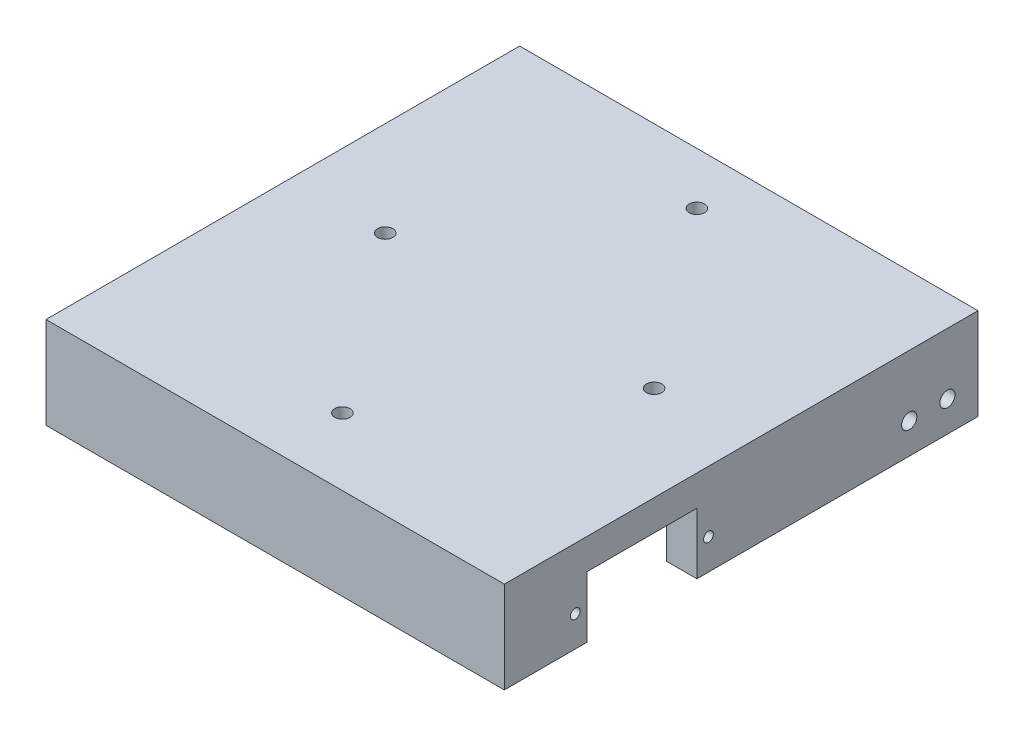
SolidWorks part; units mm, degrees
ref_plane "Front Plane" through (0, 0, 0) normal (0, 0, 1) x (1, 0, 0)
ref_plane "Top Plane" through (0, 0, 0) normal (0, 1, 0) x (1, 0, 0)
ref_plane "Right Plane" through (0, 0, 0) normal (1, 0, 0) x (0, 0, -1)
sketch "Sketch1" plane through (0, 0, 0) normal (0, 1, 0) x (1, 0, 0)
  line L1 (-47.625, -47.625) -> (47.625, -47.625)
  line L2 (-47.625, -47.625) -> (-47.625, 47.625)
  line L3 (-47.625, 47.625) -> (47.625, 47.625)
  line L4 (47.625, -47.625) -> (47.625, 47.625)
  line L5 (-47.625, -47.625) -> (47.625, 47.625) construction
  line L6 (-47.625, 47.625) -> (47.625, -47.625) construction
  point P0 (0, 0)
  dimension "D1" = 95.25
  dimension "D2" = 95.25
extrude "Boss-Extrude1" add sketch "Sketch1" along normal blind 6.35
sketch "Sketch4" plane through (0, 0, 0) normal (0, -1, 0) x (-1, 0, 0)
  line L0 (-47.625, 0) -> (-50047.625, 0) construction
  line L1 (-47.625, -47.625) -> (-47.625, 47.625) construction
  line L2 (47.625, 47.625) -> (47.625, -47.625) construction
  line L3 (-41.275, -47.625) -> (-47.625, -47.625)
  line L4 (-41.275, -47.625) -> (-41.275, 47.625)
  line L5 (-41.275, 47.625) -> (-47.625, 47.625)
  line L6 (-47.625, -47.625) -> (-47.625, 47.625)
  line L7 (-41.275, -47.625) -> (-47.625, 47.625) construction
  line L8 (-41.275, 47.625) -> (-47.625, -47.625) construction
  line L9 (41.275, -47.625) -> (47.625, -47.625)
  line L10 (41.275, -47.625) -> (41.275, 47.625)
  line L11 (41.275, 47.625) -> (47.625, 47.625)
  line L12 (47.625, -47.625) -> (47.625, 47.625)
  line L13 (41.275, -47.625) -> (47.625, 47.625) construction
  line L14 (41.275, 47.625) -> (47.625, -47.625) construction
  line L15 (47.625, -47.625) -> (-47.625, -47.625) construction
  point P4 (-47.625, 0)
  point P5 (-44.45, 0)
  point P10 (44.45, 0)
  dimension "D1" = 6.35
extrude "Boss-Extrude2" add sketch "Sketch4" along normal blind 12.7
sketch "Sketch5" plane through (-41.275, 0, 0) normal (1, 0, 0) x (0, 0, -1)
  line L0 (-22.225, -1.016) -> (-22.225, -11.684) construction
  line L1 (47.625, 0) -> (-47.625, 0) construction
  line L3 (-47.625, 6.35) -> (-47.625, -12.7) construction
  line L4 (-33.655, -12.7) -> (-10.795, -12.7)
  line L5 (-33.655, -12.7) -> (-33.655, 0)
  line L6 (-33.655, 0) -> (-10.795, 0)
  line L7 (-10.795, -12.7) -> (-10.795, 0)
  line L8 (-33.655, -12.7) -> (-10.795, 0) construction
  line L9 (-33.655, 0) -> (-10.795, -12.7) construction
  line L10 (47.625, -12.7) -> (-47.625, -12.7) construction
  point P6 (-22.225, -6.35)
  dimension "D1" = 22.86
  dimension "D2" = 25.4
extrude "Cut-Extrude1" cut sketch "Sketch5" against normal through all both and the other way through all
sketch "Sketch6" plane through (-47.625, 0, 0) normal (-1, 0, 0) x (0, 0, 1)
  line L0 (34.29, -6.35) -> (50034.29, -6.35) construction
  line L1 (33.655, 0) -> (33.655, -12.7) construction
  line L3 (10.795, 0) -> (33.655, 0) construction
  circle A0 centre (36.068, -6.35) radius 1.016
  circle A1 centre (8.382, -6.35) radius 1.016
  point P4 (33.655, -6.35)
  point P11 (22.225, 0)
  dimension "D3" = 2.032
  dimension "D1" = 27.686
  dimension "D2" = 13.843
extrude "Cut-Extrude2" cut sketch "Sketch6" against normal through all
sketch "Sketch7" plane through (0, 0, 0) normal (0, -1, 0) x (1, 0, 0)
  line L0 (0, 0) -> (50000, 0) construction
  line L1 (0, -36.83) -> (0, 36.83) construction
  circle A0 centre (27.94, 0) radius 1.5875
  circle A1 centre (-27.94, 0) radius 1.5875
  circle A2 centre (0, 36.83) radius 1.5875
  circle A3 centre (0, -36.83) radius 1.5875
  point P10 (0, 0)
  dimension "D1" = 55.88
  dimension "D3" = 3.175
  dimension "D2" = 27.94
  dimension "D4" = 73.66
extrude "Cut-Extrude3" cut sketch "Sketch7" against normal through all
sketch "Sketch8" plane through (-41.275, 0, 0) normal (1, 0, 0) x (0, 0, -1)
  line L0 (47.625, -6.35) -> (50047.625, -6.35) construction
  line L1 (47.625, -12.7) -> (47.625, 0) construction
  circle A0 centre (41.275, -6.35) radius 1.5875
  circle A1 centre (33.3375, -6.35) radius 1.5875
  point P4 (47.625, -6.35)
  point P9 (33.2786, -6.35)
  dimension "D1" = 3.175
  dimension "D2" = 6.35
  dimension "D3" = 7.9375
extrude "Cut-Extrude4" cut sketch "Sketch8" against normal through all both and the other way through all
sketch "Sketch9" plane through (0, 0, 47.625) normal (0, 0, 1) x (1, 0, 0)
  line L1 (-47.625, 6.35) -> (47.625, 6.35)
  line L2 (-47.625, 6.35) -> (-47.625, -12.7)
  line L3 (-47.625, -12.7) -> (47.625, -12.7)
  line L4 (47.625, 6.35) -> (47.625, -12.7)
extrude "Boss-Extrude3" add sketch "Sketch9" along normal blind 3.175
